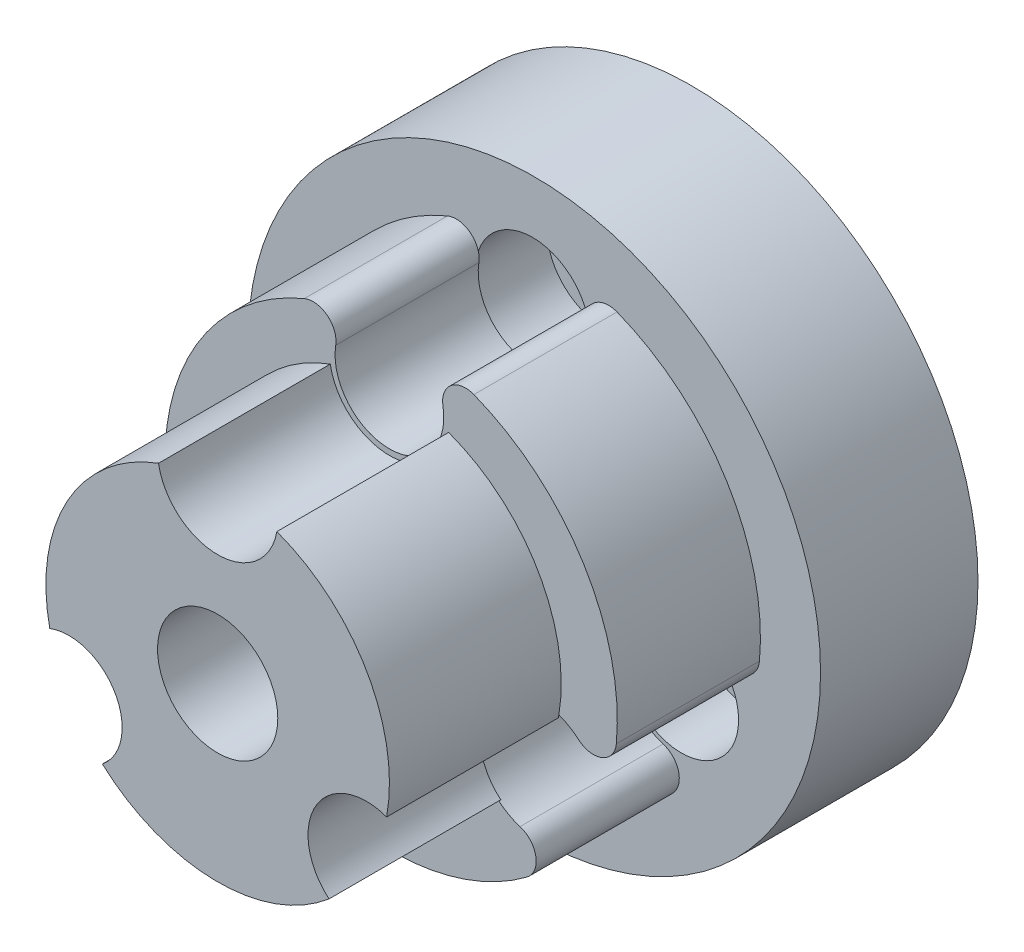
SolidWorks part; units mm, degrees
ref_plane "前视基准面" through (0, 0, 0) normal (0, 0, 1) x (1, 0, 0)
ref_plane "上视基准面" through (0, 0, 0) normal (0, 1, 0) x (1, 0, 0)
ref_plane "右视基准面" through (0, 0, 0) normal (1, 0, 0) x (0, 0, -1)
other "Configuration Table"
sketch "Sketch2" plane through (0, 0, -96.1912) normal (0, 0, 1) x (1, 0, 0)
  circle A0 centre (0, 0) radius 10
  circle A1 centre (0, 0) radius 2.1
  circle A2 centre (-0.059, 6.1331) radius 1.2
  circle A3 centre (5.1372, -2.8669) radius 1.2
  circle A4 centre (-5.2551, -2.8669) radius 1.2
  dimension "D1" = 20
  dimension "D2" = 4.2
extrude "Boss-Extrude1" add sketch "Sketch2" along normal blind 3
sketch "Sketch3" plane through (0, 0, -93.1912) normal (0, 0, 1) x (1, 0, 0)
  circle A0 centre (-5.2551, -2.8669) radius 2
  circle A1 centre (-0.059, 6.1331) radius 2
  circle A2 centre (5.1372, -2.8669) radius 2
  circle A3 centre (0, 0) radius 2.1
  circle A4 centre (0, 0) radius 10
extrude "Boss-Extrude2" add sketch "Sketch3" along normal blind 2.5
sketch "Sketch4" plane through (0, 0, -90.6912) normal (0, 0, 1) x (1, 0, 0)
  arc A0 (7.265, -3.1032) -> (0.7159, 7.8675) centre (0, 0) ccw
  circle A1 centre (0, 0) radius 2.1
  arc A2 (7.265, -3.1032) -> (6.4555, -4.5537) centre (5.1372, -2.8669) ccw
  arc A3 (-6.6682, -4.2362) -> (-7.1714, -3.3138) centre (-5.2551, -2.8669) ccw
  arc A4 (-0.867, 7.8523) -> (0.7159, 7.8675) centre (-0.059, 6.1331) ccw
  arc A5 (-6.6682, -4.2362) -> (6.4555, -4.5537) centre (0, 0) ccw
  arc A6 (-0.867, 7.8523) -> (-7.1714, -3.3138) centre (0, 0) ccw
extrude "Boss-Extrude3" add sketch "Sketch4" along normal blind 5
fillet "Fillet1" radius 0.8 6 edges at (-6.6682, -4.2362, -88.1912) (-7.1714, -3.3138, -88.1912) (0.7159, 7.8675, -88.1912) (-0.867, 7.8523, -88.1912) (6.4555, -4.5537, -88.1912) (7.265, -3.1032, -88.1912)
sketch "Sketch5" plane through (0, 0, -85.6912) normal (0, 0, 1) x (1, 0, 0)
  circle A0 centre (-0.059, 0.1331) radius 2.1
  arc A1 (5.8421, -0.9517) -> (2.0084, 5.7657) centre (-0.059, 0.1331) ccw
  arc A2 (5.8421, -0.9517) -> (3.8311, -4.435) centre (5.1372, -2.8669) ccw
  arc A3 (-4.0872, -4.3136) -> (-5.9241, -1.1321) centre (-5.2551, -2.8669) ccw
  arc A4 (-2.1263, 5.7657) -> (2.0084, 5.7657) centre (-0.059, 6.1331) ccw
  arc A5 (-4.0872, -4.3136) -> (3.8311, -4.435) centre (-0.059, 0.1331) ccw
  arc A6 (-2.1263, 5.7657) -> (-5.9241, -1.1321) centre (-0.059, 0.1331) ccw
  dimension "D1" = 12
extrude "Boss-Extrude4" add sketch "Sketch5" along normal blind 6
sketch "Sketch6" plane through (0, 0, -79.6912) normal (0, 0, 1) x (1, 0, 0)
  circle A0 centre (0, 0) radius 2.1
  arc A3 (-1.9351, 6.4308) -> (-3.0323, 7.2949) centre (-2.7252, 6.5562) ccw construction
  arc A18 (-1.9351, 6.4308) -> (1.8111, 6.4668) centre (-0.059, 6.1331) ccw construction
  arc A27 (-1.9351, 6.4308) -> (-3.0323, 7.2949) centre (-2.7252, 6.5562) ccw
  arc A42 (-1.9351, 6.4308) -> (1.8111, 6.4668) centre (-0.059, 6.1331) ccw
